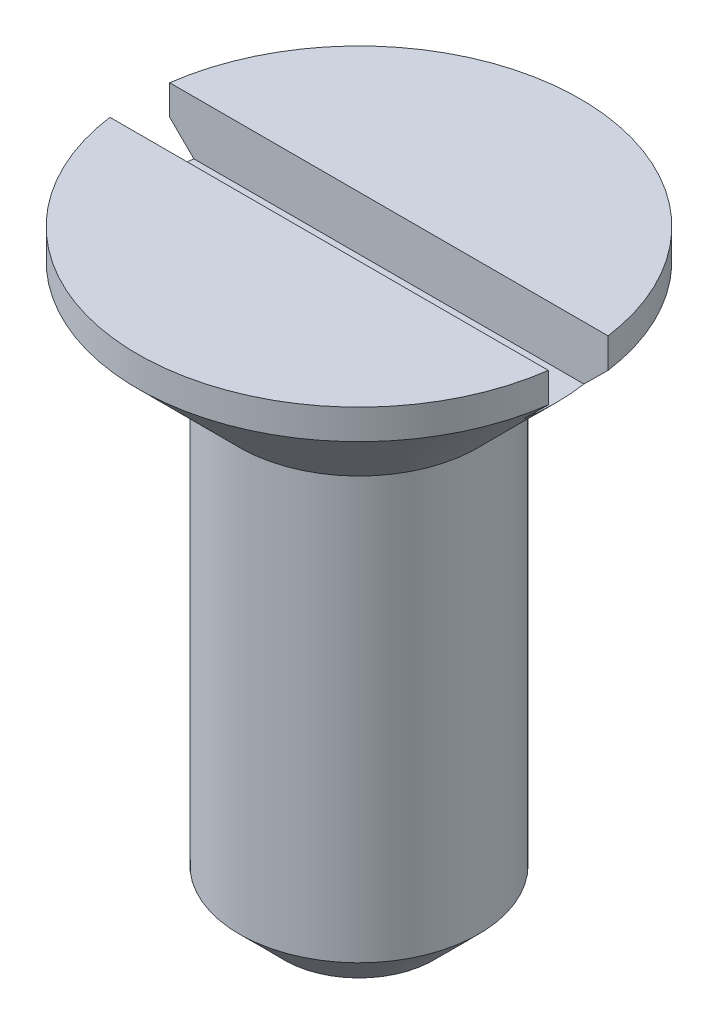
SolidWorks part; units mm, degrees
ref_plane "Спереди" through (0, 0, 0) normal (0, 0, 1) x (1, 0, 0)
ref_plane "Сверху" through (0, 0, 0) normal (0, 1, 0) x (1, 0, 0)
ref_plane "Справа" through (0, 0, 0) normal (1, 0, 0) x (0, 0, -1)
sketch "Эскиз1" plane through (0, 0, 0) normal (0, 0, 1) x (1, 0, 0)
  line L0 (0, 125.7632) -> (0, 0) construction
  line L2 (0, 92.035) -> (0, 82.035)
  line L3 (0, 92.035) -> (3.7, 92.035)
  line L4 (2, 89.835) -> (2, 82.035)
  line L5 (2, 89.835) -> (3.7, 91.535)
  line L6 (2, 82.035) -> (0, 82.035)
  line L7 (3.7, 92.035) -> (3.7, 91.535)
  dimension "D1" = 3.7
  dimension "D2" = 10
  dimension "D3" = 2.2
  dimension "D4" = 45
  dimension "D5" = 2
revolve "Повернуть1" add sketch "Эскиз1" angle 360 about L0
ref_axis "Ось4" through (0, 3.4535, 0) along (0, -1, 0)
sketch "Эскиз13" plane through (0, 92.035, 0) normal (0, 1, 0) x (-1, 0, 0)
  line L1 (3.7, -0.5) -> (-3.7, -0.5)
  line L2 (3.7, -0.5) -> (3.7, 0.5)
  line L3 (3.7, 0.5) -> (-3.7, 0.5)
  line L4 (-3.7, -0.5) -> (-3.7, 0.5)
  dimension "D1" = 3.7
  dimension "D2" = 7.4
  dimension "D3" = 0.5
  dimension "D4" = 1
extrude "Вырез-Вытянуть9" cut sketch "Эскиз13" against normal blind 0.9
chamfer "Фаска1" distance 0.75 angle 45 1 edges at (-2, 82.035, 0)
